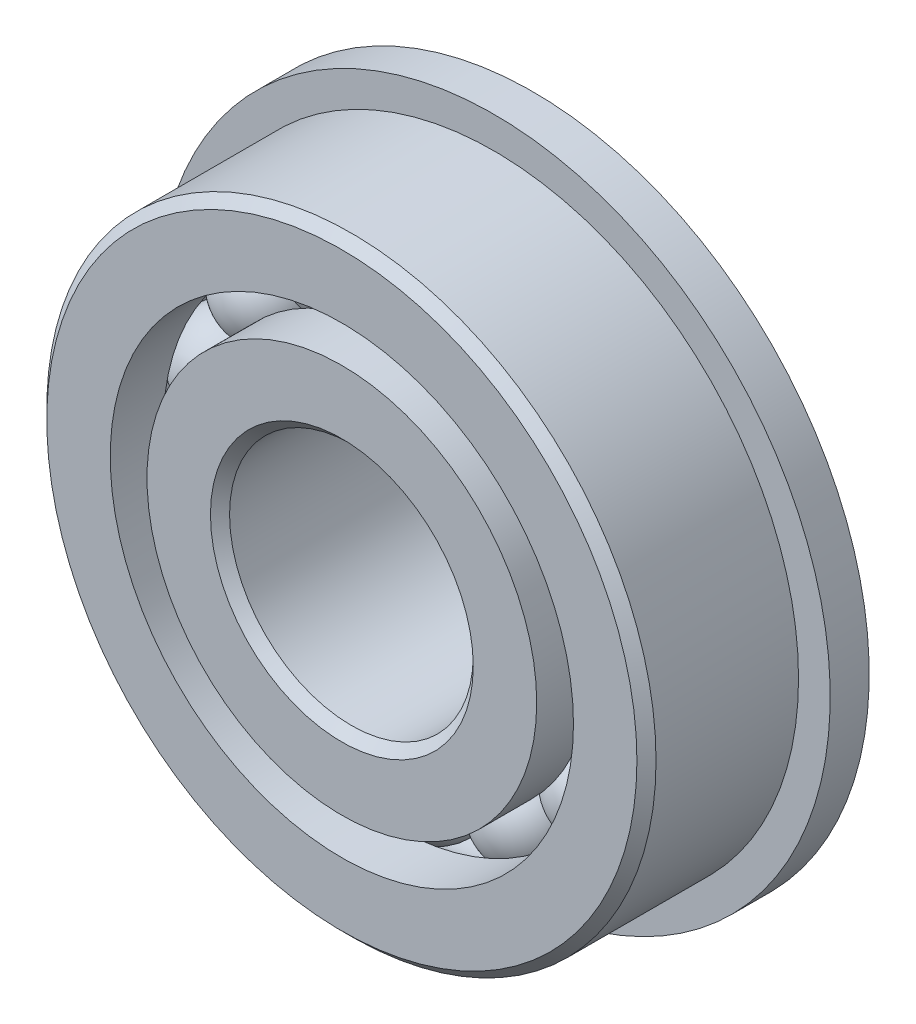
SolidWorks part; units mm, degrees
material "AISI 1020"
ref_plane "Front Plane" through (0, 0, 0) normal (0, 0, 1) x (1, 0, 0)
ref_plane "Top Plane" through (0, 0, 0) normal (0, 1, 0) x (1, 0, 0)
ref_plane "Right Plane" through (0, 0, 0) normal (1, 0, 0) x (0, 0, -1)
sketch "Sketch1" plane through (0, 0, 0) normal (1, 0, 0) x (0, 0, -1)
  line L0 (-2.4892, 0) -> (2.4892, 0) construction
  line L1 (0, 7.9375) -> (0, -7.9375) construction
  line L2 (2.2403, 7.9375) -> (-2.2403, 7.9375)
  line L3 (-2.2403, 7.9375) -> (-2.4892, 7.6886)
  line L4 (-2.4892, 7.6886) -> (-2.4892, 6.0352)
  line L5 (-2.4892, 6.0352) -> (-1.1063, 6.0352)
  line L6 (2.4892, 6.0352) -> (1.1063, 6.0352)
  line L7 (2.4892, 7.6886) -> (2.4892, 6.0352)
  line L8 (2.2403, 7.9375) -> (2.4892, 7.6886)
  line L9 (0, 7.9375) -> (0, 5.5563) construction
  line L10 (0, 5.5563) -> (0, 3.175) construction
  arc A0 (-1.1063, 6.0352) -> (1.1063, 6.0352) centre (0, 5.5563) cw
  point P14 (0, 3.175)
  dimension "D3" = 2.2126
  dimension "D1" = 45
  dimension "Width" = 4.9784
  dimension "OD" = 15.875
  dimension "D2" = 0.2489
  dimension "Shaft Dia" = 6.35
  dimension "D4" = 0.479
revolve "Revolve1" add sketch "Sketch1" angle 360 about L0
sketch "Sketch3" plane through (0, 0, 0) normal (1, 0, 0) x (0, 0, -1)
  line L0 (-2.2403, 7.9375) -> (-2.4892, 7.6886) construction
  line L1 (-1.1063, 5.0773) -> (-2.4892, 5.0773)
  line L2 (-2.4892, 7.6886) -> (-2.4892, 6.0352) construction
  line L3 (-2.4892, 5.0773) -> (-2.4892, 3.4239)
  line L5 (-2.4892, 3.4239) -> (-2.2403, 3.175)
  line L6 (-2.2403, 3.175) -> (2.2403, 3.175)
  line L7 (2.4892, 7.6886) -> (2.4892, 6.0352) construction
  line L8 (2.2403, 3.175) -> (2.4892, 3.4239)
  line L10 (2.4892, 3.4239) -> (2.4892, 5.0773)
  line L11 (2.4892, 5.0773) -> (1.1063, 5.0773)
  line L13 (2.2403, 7.9375) -> (2.4892, 7.6886) construction
  arc A1 (1.1063, 5.0773) -> (-1.1063, 5.0773) centre (0, 5.5562) cw
  arc A2 (1.1063, 6.0352) -> (-1.1063, 6.0352) centre (0, 5.5563) ccw construction
revolve "Revolve3" add sketch "Sketch3" angle 360 about L0
sketch "Sketch5" plane through (0, 0, 0) normal (1, 0, 0) x (0, 0, -1)
  line L0 (2.4892, 7.6886) -> (2.4892, 6.0352) construction
  line L1 (2.4892, 6.8619) -> (1.4732, 6.8619)
  line L2 (2.4892, 6.8619) -> (2.4892, 8.763)
  line L3 (2.4892, 8.763) -> (1.4732, 8.763)
  line L4 (1.4732, 6.8619) -> (1.4732, 8.763)
  line L5 (2.4892, 0) -> (-2.4892, 0) construction
  dimension "Th" = 1.016
  dimension "Flange OD" = 17.526
revolve "Revolve5" add sketch "Sketch5" angle 360 about L5
sketch "Sketch4" plane through (0, 0, 0) normal (1, 0, 0) x (0, 0, -1)
  line L0 (-1.2055, 5.5563) -> (1.2055, 5.5563)
  arc A2 (-1.2055, 5.5563) -> (1.2055, 5.5563) centre (0, 5.5563) cw
  arc A3 (1.1063, 6.0352) -> (-1.1063, 6.0352) centre (0, 5.5563) ccw construction
revolve "Revolve4" add sketch "Sketch4" angle 360 about L0
ref_axis "Axis1" through (0, 0, -2.4892) along (0, 0, 1)
pattern_circular "CirPattern1" count 14 every 25.714 about axis through (0, 0, -2.4892) along (0, 0, 1) of bodies 104
equation "\"D2@Sketch1\" = \"Width@Sketch1\"*.05"
equation "\"D3@Sketch1\" = \"Width@Sketch1\"/2.25"
equation "\"D4@Sketch1\" = (((\"OD@Sketch1\"-\"Width@Sketch1\")/2)/3.25)/3.5"
equation "\"D2@CirPattern1\" = 360/\"Balls@CirPattern1\""
